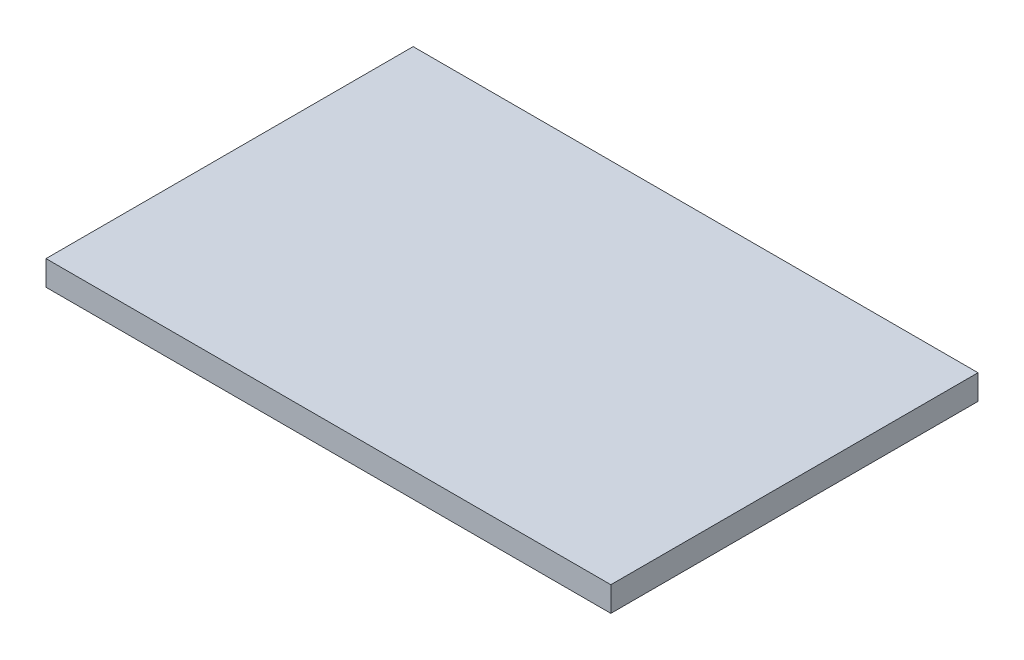
SolidWorks part; units mm, degrees
ref_plane "Front Plane" through (0, 0, 0) normal (0, 0, 1) x (1, 0, 0)
ref_plane "Top Plane" through (0, 0, 0) normal (0, 1, 0) x (1, 0, 0)
ref_plane "Right Plane" through (0, 0, 0) normal (1, 0, 0) x (0, 0, -1)
sketch "Sketch1" plane through (0, 0, 0) normal (0, 1, 0) x (1, 0, 0)
  line L1 (-63.5, -41.275) -> (63.5, -41.275)
  line L2 (-63.5, -41.275) -> (-63.5, 41.275)
  line L3 (-63.5, 41.275) -> (63.5, 41.275)
  line L4 (63.5, -41.275) -> (63.5, 41.275)
  line L5 (-63.5, -41.275) -> (63.5, 41.275) construction
  line L6 (-63.5, 41.275) -> (63.5, -41.275) construction
  point P0 (0, 0)
  dimension "D1" = 127
  dimension "D2" = 82.55
extrude "Boss-Extrude1" add sketch "Sketch1" along normal blind 5.588
